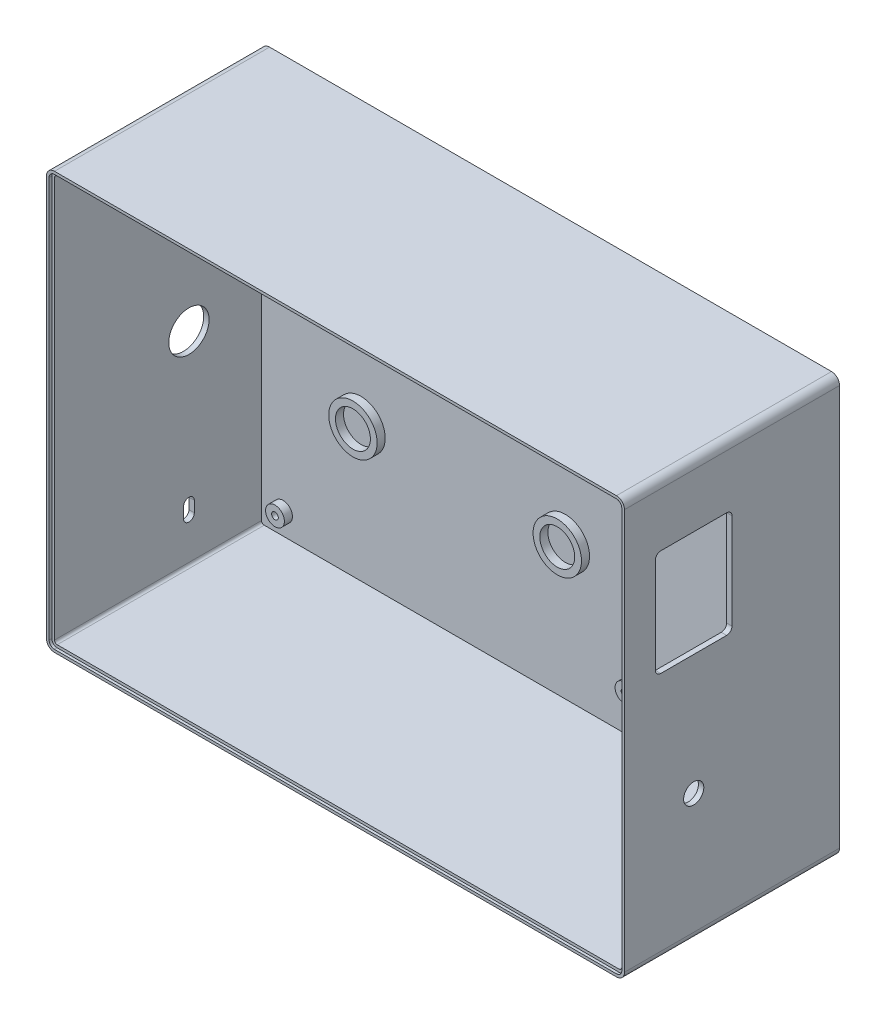
SolidWorks part; units mm, degrees
ref_plane "前视基准面" through (0, 0, 0) normal (0, 0, 1) x (1, 0, 0)
ref_plane "上视基准面" through (0, 0, 0) normal (0, 1, 0) x (1, 0, 0)
ref_plane "右视基准面" through (0, 0, 0) normal (1, 0, 0) x (0, 0, -1)
other "Configuration Table"
sketch "草图1" plane through (0, 0, 0) normal (0, 0, 1) x (1, 0, 0)
  line L1 (0, 0) -> (215, 0)
  line L2 (0, 0) -> (0, -155)
  line L3 (0, -155) -> (215, -155)
  line L4 (215, 0) -> (215, -155)
  dimension "D1" = 155
  dimension "D2" = 215
extrude "凸台-拉伸1" add sketch "草图1" along normal blind 80
fillet "圆角1" radius 3 4 edges at (0, -155, 40) (215, -155, 40) (215, 0, 40) (0, 0, 40)
shell "抽壳1" thickness 2 removed face at (107.5, -77.5, 80)
sketch "草图2" plane through (0, 0, 2) normal (0, 0, 1) x (1, 0, 0)
  line L0 (213, -77.5) -> (2, -77.5) construction
  line L1 (213, -152) -> (213, -3) construction
  line L2 (2, -3) -> (2, -152) construction
  line L3 (213, -152) -> (213, -3) construction
  circle A0 centre (207, -20) radius 3.5
  circle A1 centre (142, -20) radius 3.5
  circle A2 centre (142, -135) radius 3.5
  circle A3 centre (207, -135) radius 3.5
  circle A4 centre (207, -20) radius 1.25
  circle A5 centre (142, -20) radius 1.25
  circle A6 centre (142, -135) radius 1.25
  circle A7 centre (207, -135) radius 1.25
  dimension "D2" = 7
  dimension "D6" = 2.5
  dimension "D1" = 57.5
  dimension "D3" = 6
  dimension "D4" = 2
  dimension "D5" = 2
  dimension "D7" = 2
  dimension "D8" = 2
extrude "凸台-拉伸2" add sketch "草图2" along normal blind 5
sketch "草图3" plane through (0, 0, 2) normal (0, 0, 1) x (1, 0, 0)
  line L0 (212, -2) -> (3, -2) construction
  circle A0 centre (115, -52.5) radius 6.5
  circle A1 centre (115, -52.5) radius 9
  circle A2 centre (142, -20) radius 1.25 construction
  circle A3 centre (39, -52.5) radius 6.5
  circle A4 centre (39, -52.5) radius 9
  circle A5 centre (39, -102.5) radius 6.5
  circle A6 centre (39, -102.5) radius 9
  circle A7 centre (115, -102.5) radius 6.5
  circle A8 centre (115, -102.5) radius 9
  dimension "D1" = 13
  dimension "D2" = 18
  dimension "D3" = 27
  dimension "D6" = 50.5
  dimension "D4" = 2
  dimension "D5" = 2
extrude "凸台-拉伸3" add sketch "草图3" along normal blind 3
sketch "草图4" plane through (215, 0, 0) normal (1, 0, 0) x (0, 0, -1)
  line L0 (0, -152) -> (0, -3) construction
  line L1 (-68.5, -23) -> (-40, -23)
  line L2 (-68.5, -23) -> (-68.5, -62.5)
  line L3 (-68.5, -62.5) -> (-40, -62.5)
  line L4 (-40, -23) -> (-40, -62.5)
  line L5 (0, -3) -> (-80, -3) construction
  dimension "D1" = 28.5
  dimension "D2" = 39.5
  dimension "D3" = 40
  dimension "D4" = 20
extrude "切除-拉伸3" cut sketch "草图4" against normal blind 3
fillet "圆角2" radius 2 4 edges at (214, -62.5, 40) (214, -62.5, 68.5) (214, -23, 68.5) (214, -23, 40)
sketch "草图5" plane through (0, 0, 0) normal (-1, 0, 0) x (0, 0, 1)
  line L0 (0, -77.5) -> (80, -77.5) construction
  line L1 (0, -3) -> (0, -152) construction
  line L2 (80, -3) -> (80, -152) construction
  circle A0 centre (29, -77.5) radius 7.5
  dimension "D1" = 15
  dimension "D2" = 29
extrude "切除-拉伸4" cut sketch "草图5" against normal blind 3
sketch "草图6" plane through (215, 0, 0) normal (1, 0, 0) x (0, 0, -1)
  line L0 (-54.25, -62.5) -> (-54.25, -152) construction
  line L1 (-66.5, -62.5) -> (-42, -62.5) construction
  line L2 (-80, -152) -> (0, -152) construction
  circle A0 centre (-54.25, -107.25) radius 3.75
  dimension "D1" = 7.5
extrude "切除-拉伸5" cut sketch "草图6" against normal blind 3
sketch "草图7" plane through (0, 0, 0) normal (-1, 0, 0) x (0, 0, 1)
  line L0 (29, -77.5) -> (29, -152) construction
  line L1 (0, -152) -> (80, -152) construction
  line L2 (29, -133) -> (29, -137) construction
  line L3 (31, -133) -> (31, -137)
  line L4 (27, -133) -> (27, -137)
  arc A1 (31, -133) -> (27, -133) centre (29, -133) ccw
  arc A2 (27, -137) -> (31, -137) centre (29, -137) ccw
  point P7 (29, -135)
  dimension "D1" = 4
  dimension "D2" = 2
  dimension "D3" = 15
extrude "切除-拉伸6" cut sketch "草图7" against normal blind 3
sketch "草图8" plane through (0, 0, 80) normal (0, 0, 1) x (1, 0, 0)
  line L0 (3, -154) -> (212, -154)
  line L1 (214, -152) -> (214, -3)
  line L2 (212, -1) -> (3, -1)
  line L3 (1, -3) -> (1, -152)
  line L4 (3, -153) -> (212, -153)
  line L5 (213, -152) -> (213, -3)
  line L6 (212, -2) -> (3, -2)
  line L7 (2, -3) -> (2, -152)
  line L8 (3, -153) -> (212, -153)
  line L9 (213, -152) -> (213, -3)
  line L10 (212, -2) -> (3, -2)
  line L11 (2, -3) -> (2, -152)
  arc A0 (212, -154) -> (214, -152) centre (212, -152) ccw
  arc A1 (214, -3) -> (212, -1) centre (212, -3) ccw
  arc A2 (3, -1) -> (1, -3) centre (3, -3) ccw
  arc A3 (1, -152) -> (3, -154) centre (3, -152) ccw
  arc A4 (212, -153) -> (213, -152) centre (212, -152) ccw
  arc A5 (213, -3) -> (212, -2) centre (212, -3) ccw
  arc A6 (3, -2) -> (2, -3) centre (3, -3) ccw
  arc A7 (2, -152) -> (3, -153) centre (3, -152) ccw
  arc A8 (212, -153) -> (213, -152) centre (212, -152) ccw
  arc A9 (213, -3) -> (212, -2) centre (212, -3) ccw
  arc A10 (3, -2) -> (2, -3) centre (3, -3) ccw
  arc A11 (2, -152) -> (3, -153) centre (3, -152) ccw
  dimension "D1" = 0
  dimension "D2" = 1
extrude "切除-拉伸7" cut sketch "草图8" against normal blind 1
sketch "草图9" plane through (0, 0, 2) normal (0, 0, 1) x (1, 0, 0)
  line L0 (212, 0) -> (3, 0) construction
  line L1 (0, -3) -> (0, -152) construction
  circle A0 centre (10, -10) radius 3.5
  circle A1 centre (205, -10) radius 3.5
  circle A2 centre (205, -145) radius 3.5
  circle A3 centre (10, -145) radius 3.5
  dimension "D1" = 7
  dimension "D2" = 10
  dimension "D3" = 10
  dimension "D4" = 2
  dimension "D5" = 2
extrude "凸台-拉伸4" add sketch "草图9" along normal blind 3
sketch "草图10" plane through (0, 0, 5) normal (0, 0, 1) x (1, 0, 0)
  circle A0 centre (10, -10) radius 1.25
  circle A1 centre (205, -10) radius 1.25
  circle A2 centre (205, -145) radius 1.25
  circle A3 centre (10, -145) radius 1.25
  dimension "D1" = 2.5
  dimension "D2" = 2
  dimension "D3" = 2
extrude "切除-拉伸8" cut sketch "草图10" against normal blind 5
